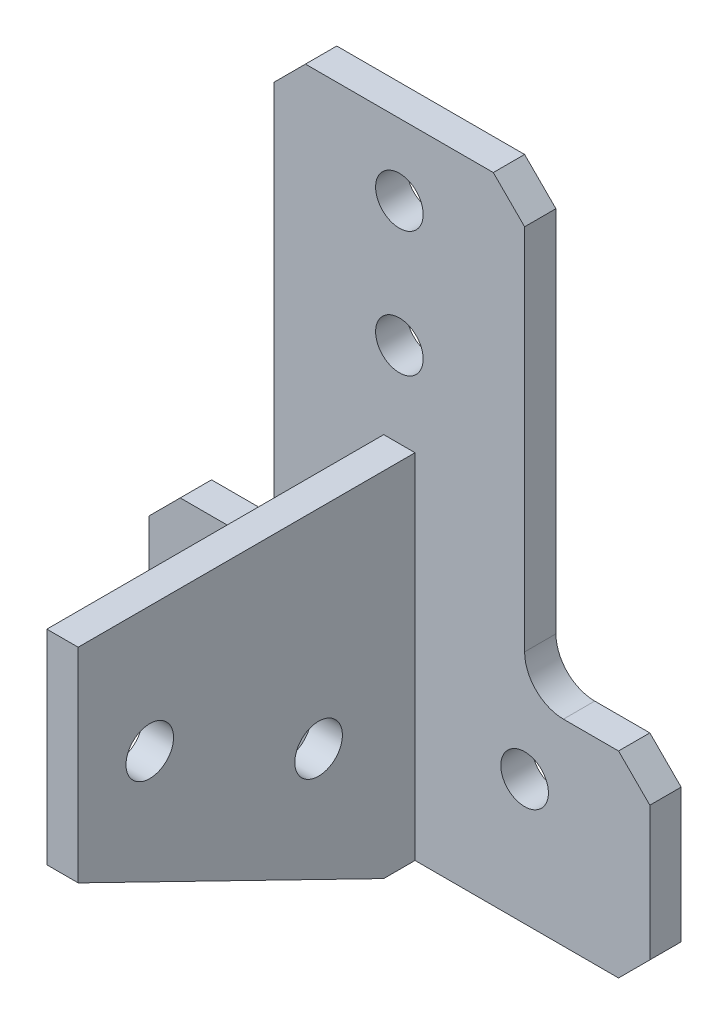
SolidWorks part; units mm, degrees
ref_plane "Front Plane" through (0, 0, 0) normal (0, 0, 1) x (1, 0, 0)
ref_plane "Top Plane" through (0, 0, 0) normal (0, 1, 0) x (1, 0, 0)
ref_plane "Right Plane" through (0, 0, 0) normal (1, 0, 0) x (0, 0, -1)
sketch "Sketch1" plane through (0, 0, 0) normal (0, 1, 0) x (1, 0, 0)
  line L0 (3.175, 47.625) -> (26.9875, 47.625)
  line L1 (0, 0) -> (3.175, 0)
  line L2 (0, 0) -> (0, 47.625)
  line L4 (3.175, 0) -> (3.175, 47.625)
  line L7 (-23.8125, 47.625) -> (0, 47.625)
  line L8 (-23.8125, 47.625) -> (-23.8125, 50.8)
  line L9 (-23.8125, 50.8) -> (26.9875, 50.8)
  line L10 (26.9875, 47.625) -> (26.9875, 50.8)
  point P0 (0, 0)
  point P1 (0, 0)
  point P3 (0, 0)
  point P6 (0, 24.0524)
  dimension "D1" = 50.8
  dimension "D2" = 3.175
  dimension "D3" = 3.175
  dimension "D4" = 50.8
extrude "Boss-Extrude1" add sketch "Sketch1" along normal blind 64.389
sketch "Sketch4" plane through (0, 0, -47.625) normal (0, 0, 1) x (1, 0, 0)
  line L0 (1.5875, 0) -> (1.5875, 64.389) construction
  line L1 (0, 0) -> (3.175, 0) construction
  line L2 (0, 64.389) -> (3.175, 64.389) construction
  line L3 (-23.8125, 0) -> (0, 0) construction
  line L4 (3.175, 0) -> (26.9875, 0) construction
  circle A0 centre (14.2875, 12.7) radius 2.413
  circle A1 centre (-11.1125, 12.7) radius 2.413
  dimension "D3" = 12.7
  dimension "D5" = 4.826
  dimension "D6" = 4.826
  dimension "D1" = 12.7
  dimension "D2" = 12.7
  dimension "D4" = 12.7
sketch "Sketch7" plane through (0, 0, 0) normal (-1, 0, 0) x (0, 0, 1)
  line L0 (0, 64.389) -> (0, 0) construction
  line L1 (-47.625, 64.389) -> (0, 64.389)
  line L2 (-47.625, 64.389) -> (-47.625, 35.814)
  line L3 (-47.625, 35.814) -> (0, 35.814)
  line L4 (0, 64.389) -> (0, 35.814)
  line L5 (-47.625, 0) -> (0, 0) construction
  dimension "D1" = 35.814
extrude "Cut-Extrude1" cut sketch "Sketch7" against normal through all and the other way through all
sketch "Sketch8" plane through (0, 0, -47.625) normal (0, 0, 1) x (1, 0, 0)
  line L1 (26.9875, 64.389) -> (14.2875, 64.389)
  line L2 (26.9875, 64.389) -> (26.9875, 19.939)
  line L3 (26.9875, 19.939) -> (14.2875, 19.939)
  line L4 (14.2875, 64.389) -> (14.2875, 19.939)
  line L5 (-23.8125, 64.389) -> (-11.1125, 64.389)
  line L6 (-23.8125, 64.389) -> (-23.8125, 19.939)
  line L7 (-23.8125, 19.939) -> (-11.1125, 19.939)
  line L8 (-11.1125, 64.389) -> (-11.1125, 19.939)
  dimension "D1" = 12.7
  dimension "D2" = 44.45
extrude "Cut-Extrude2" cut sketch "Sketch8" against normal through all
chamfer "Chamfer1" distance 44.45 angle 26 1 edges at (1.5875, 0, 0) first distance on face at (1.5875, 0, -36.5125)
sketch "Sketch9" plane through (0, 0, -47.625) normal (0, 0, 1) x (1, 0, 0)
  line L0 (1.5875, 0) -> (1.5875, 64.389) construction
  line L1 (-11.1125, 64.389) -> (14.2875, 64.389) construction
  circle A0 centre (1.5875, 57.15) radius 2.413
  circle A1 centre (1.5875, 44.45) radius 2.413
  point P8 (0, 0)
  dimension "D1" = 7.239
  dimension "D3" = 4.826
  dimension "D4" = 4.826
  dimension "D2" = 12.7
extrude "Cut-Extrude3" cut sketch "Sketch4" against normal through all
extrude "Cut-Extrude5" cut sketch "Sketch9" against normal through all
sketch "Sketch10" plane through (3.175, 0, 0) normal (1, 0, 0) x (0, 0, -1)
  line L0 (50.8, 64.389) -> (50.8, 19.939) construction
  line L1 (44.45, 0) -> (47.625, 0) construction
  line L2 (37.846, 14.7091) -> (20.724, 23.0601) construction
  line L3 (47.625, 35.814) -> (47.625, 0) construction
  line L4 (13.462, 35.814) -> (13.462, 15.1139)
  line L5 (47.625, 35.814) -> (0, 35.814) construction
  line L6 (0, 21.6797) -> (44.45, 0) construction
  line L7 (0, 35.814) -> (0, 21.6797) construction
  line L8 (13.462, 35.814) -> (0, 35.814)
  line L9 (0, 35.814) -> (0, 21.6797)
  line L10 (0, 21.6797) -> (13.462, 15.1139)
  circle A0 centre (37.846, 14.7091) radius 2.413
  circle A1 centre (20.724, 23.0601) radius 2.413
  dimension "D2" = 14.7091
  dimension "D5" = 4.826
  dimension "D6" = 4.826
  dimension "D1" = 12.954
  dimension "D3" = 64
  dimension "D4" = 19.05
  dimension "D7" = 13.462
extrude "Cut-Extrude6" cut sketch "Sketch10" against normal through all
fillet "Fillet1" radius 3.937 2 edges at (-11.1125, 19.939, -49.2125) (14.2875, 19.939, -49.2125)
chamfer "Chamfer2" distance 3.175 angle 45 6 edges at (-11.1125, 64.389, -49.2125) (14.2875, 64.389, -49.2125) (26.9875, 19.939, -49.2125) (26.9875, 0, -49.2125) (-23.8125, 0, -49.2125) (-23.8125, 19.939, -49.2125)
